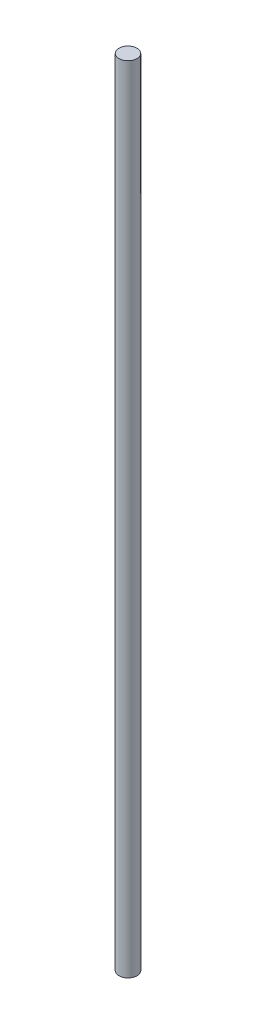
SolidWorks part; units mm, degrees
ref_plane "Front Plane" through (0, 0, 0) normal (0, 0, 1) x (1, 0, 0)
ref_plane "Top Plane" through (0, 0, 0) normal (0, 1, 0) x (1, 0, 0)
ref_plane "Right Plane" through (0, 0, 0) normal (1, 0, 0) x (0, 0, -1)
sketch "Sketch1" plane through (0, 0, 0) normal (0, 1, 0) x (1, 0, 0)
  circle A0 centre (0, 0) radius 2.5
  dimension "D1" = 5
extrude "Boss-Extrude1" add sketch "Sketch1" along normal blind 220
